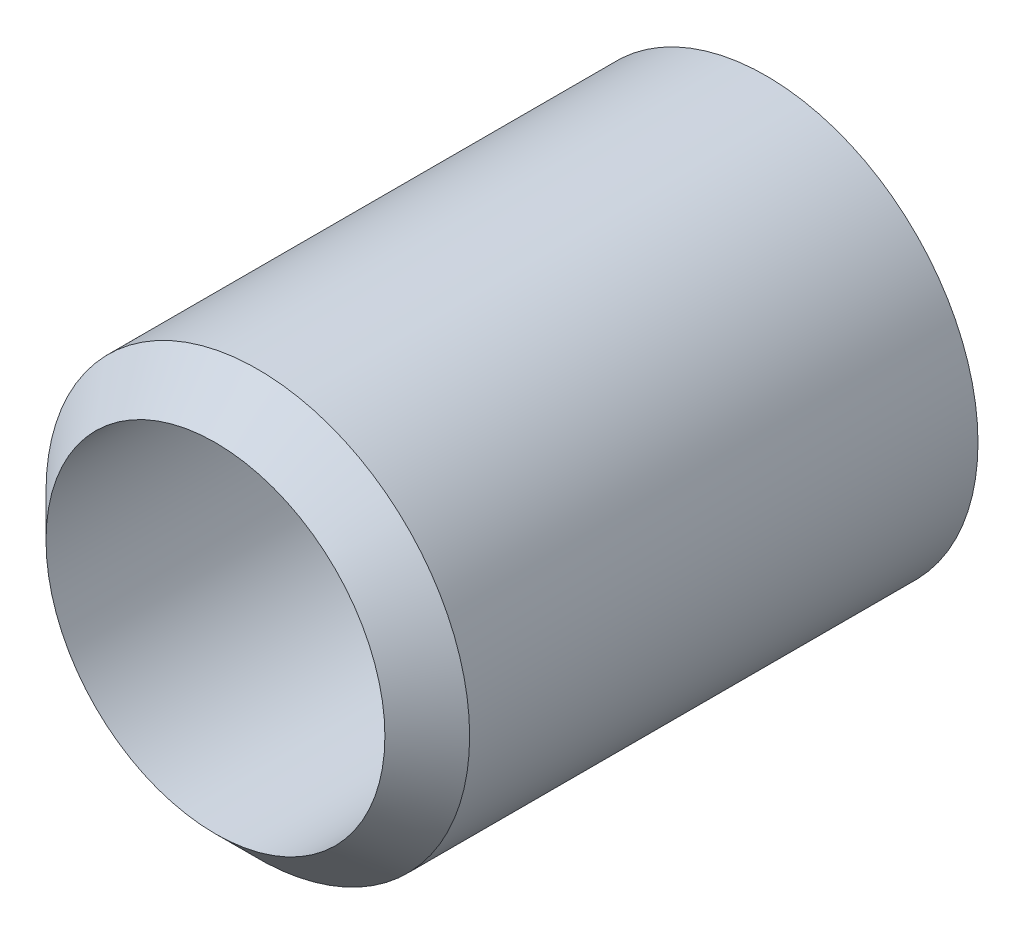
SolidWorks part; units mm, degrees
ref_plane "Front" through (0, 0, 0) normal (0, 0, 1) x (1, 0, 0)
ref_plane "Top" through (0, 0, 0) normal (0, 1, 0) x (1, 0, 0)
ref_plane "Right" through (0, 0, 0) normal (1, 0, 0) x (0, 0, -1)
sketch "Sketch2" plane through (0, 0, 0) normal (0, 0, 1) x (1, 0, 0)
  circle A0 centre (0, 0) radius 7.62
  circle A1 centre (0, 0) radius 9.525
  dimension "D1" = 15.24
  dimension "D2" = 19.05
extrude "Boss-Extrude1" add sketch "Sketch2" along normal blind 25.4
fillet "Chamfer1" radius 2.54 1 edges at (9.525, 0, 25.4) profile chamfer
